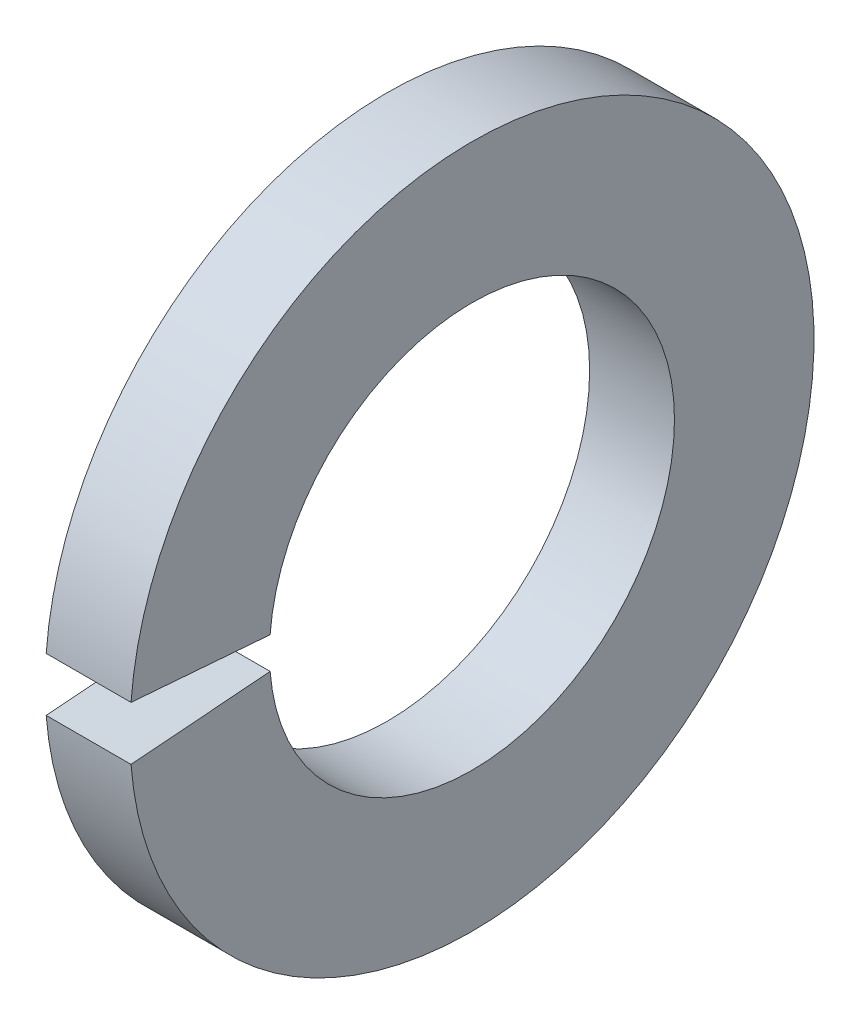
SolidWorks part; units mm, degrees
material "Chrome Stainless Steel"
ref_plane "Front Plane" through (0, 0, 0) normal (0, 0, 1) x (1, 0, 0)
ref_plane "Top Plane" through (0, 0, 0) normal (0, 1, 0) x (1, 0, 0)
ref_plane "Right Plane" through (0, 0, 0) normal (1, 0, 0) x (0, 0, -1)
ref_plane "Plane1" through (0, 0, 0) normal (0, 0.9969, 0.0785) x (-1, 0, 0)
sketch "Sketch1" plane through (0, 0, 0) normal (0, 0.9969, 0.0785) x (-1, 0, 0)
  line L0 (0.7874, 3.175) -> (0, 3.175)
  line L1 (0, 3.175) -> (0, 1.8796)
  line L2 (0, 1.8796) -> (0.7874, 1.8796)
  line L3 (0.7874, 1.8796) -> (0.7874, 3.175)
  line L4 (0, 0) -> (0.7874, 0) construction
revolve "Revolve1" add sketch "Sketch1" angle 351 about L4 reverse direction yes
